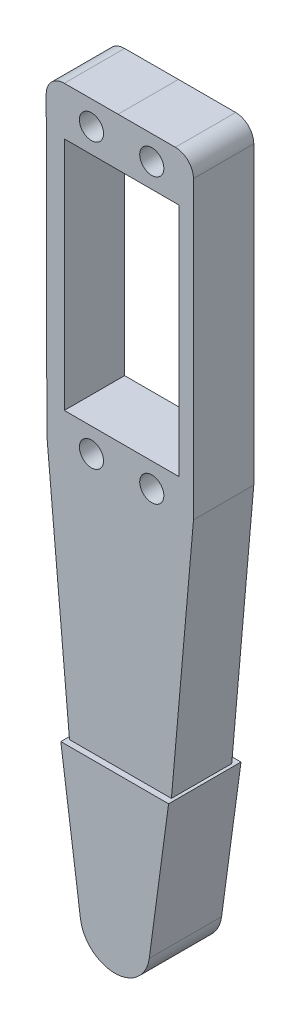
SolidWorks part; units mm, degrees
ref_plane "Plan de face" through (0, 0, 0) normal (0, 0, 1) x (1, 0, 0)
ref_plane "Plan de dessus" through (0, 0, 0) normal (0, 1, 0) x (1, 0, 0)
ref_plane "Plan de droite" through (0, 0, 0) normal (1, 0, 0) x (0, 0, -1)
sketch "Esquisse1" plane through (0, 0, 0) normal (0, 0, 1) x (1, 0, 0)
  line L0 (-0.5818, 80.2332) -> (11.9182, 80.2332)
  line L1 (11.9182, 80.2332) -> (11.9182, 28.2332)
  line L2 (11.9182, 28.2332) -> (8.2577, -13.607)
  line L3 (8.2577, -13.607) -> (7.2577, -13.6081)
  line L4 (7.2577, -13.6081) -> (3.5, -40.3453)
  line L5 (3.5, -40.3453) -> (0, -40.3453)
  line L6 (-0.1331, -67.6927) -> (-0.3132, 95.4666) construction
  line L7 (-7.6433, -13.6245) -> (-3.8266, -40.3534)
  line L8 (-8.6433, -13.6256) -> (-7.6433, -13.6245)
  line L9 (-12.3962, 28.2064) -> (-8.6433, -13.6256)
  line L10 (-12.511, 80.2062) -> (-12.3962, 28.2064)
  line L11 (-0.5818, 80.2332) -> (-12.511, 80.2062)
  line L12 (-3.8266, -40.3534) -> (0, -40.3453)
  dimension "D1" = 12.5
  dimension "D2" = 52
  dimension "D3" = 42
  dimension "D4" = 27
  dimension "D5" = 3.5
  dimension "D6" = 175
  dimension "D7" = 1
  dimension "D8" = 98
  dimension "D9" = 90
extrude "Boss.-Extru.1" add sketch "Esquisse1" along normal blind 10
sketch "Esquisse2" plane through (0, 0, 10) normal (0, 0, 1) x (1, 0, 0)
  line L1 (-9.5, 72.2332) -> (9.5, 72.2332)
  line L2 (-9.5, 72.2332) -> (-9.5, 33.2332)
  line L3 (-9.5, 33.2332) -> (9.5, 33.2332)
  line L4 (9.5, 72.2332) -> (9.5, 33.2332)
  line L9 (0, 105.7176) -> (0, -49.6248) construction
  line L10 (11.9182, 80.2332) -> (-0.5818, 80.2332) construction
  dimension "D1" = 39
  dimension "D2" = 19
  dimension "D3" = 8
  dimension "D4" = 9.5
extrude "Enlèv. mat.-Extru.1" cut sketch "Esquisse2" against normal blind 14
sketch "Esquisse3" plane through (0, 0, 0) normal (0, 0, 1) x (1, 0, 0)
  line L0 (0, 90.1205) -> (0, -48.7066) construction
  line L1 (9.5, 72.2332) -> (-9.5, 72.2332) construction
  line L2 (-9.5, 33.2332) -> (9.5, 33.2332) construction
  circle A0 centre (5, 76.2332) radius 2
  circle A1 centre (5, 29.2332) radius 2
  circle A2 centre (-5, 29.2332) radius 2
  circle A3 centre (-5, 76.2332) radius 2
  dimension "D1" = 4
  dimension "D2" = 4
  dimension "D3" = 4
  dimension "D4" = 4
  dimension "D5" = 5
  dimension "D6" = 5
extrude "Enlèv. mat.-Extru.2" cut sketch "Esquisse3" along normal blind 15 and the other way blind 7
fillet "Congé1" radius 3 1 edges at (11.9182, 80.2332, 5) type face fillet first side face at (5.6682, 80.2332, 5) second side face at (11.9182, 54.2332, 5)
fillet "Congé2" radius 3 1 edges at (-12.511, 80.2062, 5) type face fillet first side face at (-6.5464, 80.2197, 5) second side face at (-12.4536, 54.2063, 5)
sketch "Esquisse4" plane through (0, 0, 0) normal (0, 0, -1) x (-1, 0, 0)
  line L0 (-8.7926, -13.6075) -> (9.081, -13.6075)
  line L1 (9.081, -13.6075) -> (5.1417, -42.4047)
  line L2 (5.1417, -42.4047) -> (-4.9121, -42.4047)
  line L3 (-4.9121, -42.4047) -> (-8.7926, -13.6075)
extrude "Boss.-Extru.4" add sketch "Esquisse4" against normal blind 11 and the other way blind 1
fillet "Congé4" 2 edges at (4.9121, -42.4047, 5) (-5.1417, -42.4047, 5) type full round first side face at (6.8524, -28.0061, 5) second side face at (-7.1113, -28.0061, 5) middle face at (-0.1148, -42.4047, 5)
